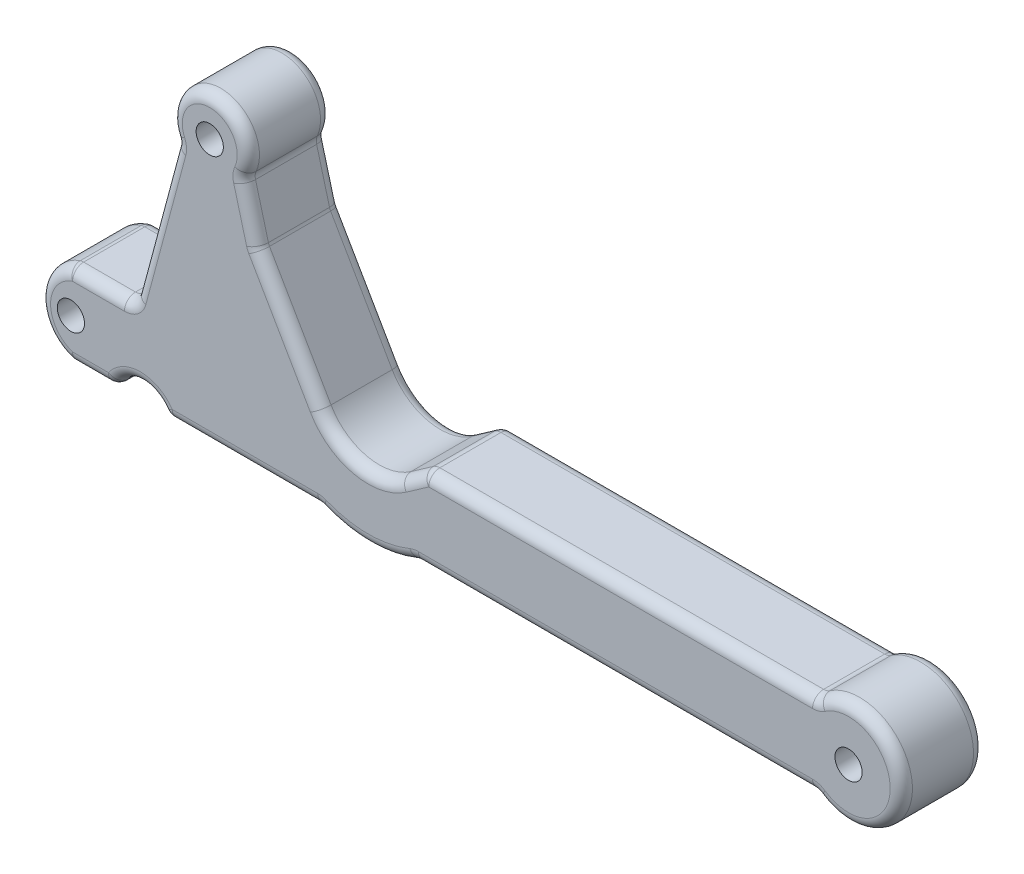
SolidWorks part; units mm, degrees
ref_plane "Front Plane" through (0, 0, 0) normal (0, 0, 1) x (1, 0, 0)
ref_plane "Top Plane" through (0, 0, 0) normal (0, 1, 0) x (1, 0, 0)
ref_plane "Right Plane" through (0, 0, 0) normal (1, 0, 0) x (0, 0, -1)
sketch "Sketch2" plane through (0, 0, 0) normal (0, 0, 1) x (1, 0, 0)
  line L0 (-88.9, 0) -> (88.9, 0) construction
  line L5 (88.9, 0) -> (-88.9, 0) construction
  line L6 (-88.9, 9.525) -> (88.9, 9.525)
  line L7 (-88.9, -9.525) -> (88.9, -9.525)
  line L8 (-63.2223, 52.4271) -> (-74.7179, 9.525)
  line L10 (-39.5821, 9.525) -> (-51.0777, 52.4271)
  line L11 (-46.1887, 34.1811) -> (-31.9535, 9.525)
  line L12 (-13.6706, 5.4718) -> (-7.882, 9.525)
  circle A8 centre (-88.9, 0) radius 3.1115
  circle A9 centre (88.9, 0) radius 3.1115
  circle A10 centre (-57.15, 50.8) radius 3.1115
  arc A11 (-88.9, 9.525) -> (-88.9, -9.525) centre (-88.9, 0) ccw
  arc A12 (88.9, -9.525) -> (88.9, 9.525) centre (88.9, 0) ccw
  arc A13 (-63.2223, 52.4271) -> (-51.0777, 52.4271) centre (-57.15, 50.8) cw
  arc A14 (-78.8449, -9.525) -> (-67.2051, -9.525) centre (-73.025, -12.065) cw
  arc A15 (79.375, -9.525) -> (69.215, -9.525) centre (74.295, -13.335) ccw
  arc A16 (-31.9535, 9.525) -> (-9.9565, 9.525) centre (-20.955, 15.875) ccw
  arc A17 (-88.9, -9.525) -> (-88.9, 9.525) centre (-86.1791, 0) cw
  arc A18 (88.9, -9.525) -> (88.9, 9.525) centre (86.1791, 0) ccw construction
  arc A19 (-31.9535, -9.525) -> (-9.9565, -9.525) centre (-20.955, 15.875) ccw
  arc A20 (81.4947, -9.525) -> (81.4947, 9.525) centre (88.9, 0) ccw
  arc A21 (-64.8259, 46.4425) -> (-49.4741, 46.4425) centre (-57.15, 50.8) cw
  point P5 (0, 0)
  point P8 (0, 0)
  point P30 (-20.955, 3.175)
  dimension "D1" = 6.223
  dimension "D9" = 6.35
  dimension "D11" = 6.35
  dimension "D16" = 12.7
  dimension "D18" = 9.906
  dimension "D2" = 177.8
  dimension "D3" = 31.75
  dimension "D4" = 50.8
  dimension "D5" = 19.05
  dimension "D6" = 3.175
  dimension "D7" = 75
  dimension "D8" = 15.875
  dimension "D10" = 2.54
  dimension "D12" = 3.81
  dimension "D13" = 14.605
  dimension "D14" = 6.35
  dimension "D15" = 67.945
  dimension "D17" = 35
  dimension "D19" = 2.54
  dimension "D20" = 2.54
extrude "Boss-Extrude1" add sketch "Sketch2" along normal mid plane 19.05 contours L7 A18 L6 L12 A16 A17 A14 A15 A8 A9 | L6 A16 | A16 L12 L6 | L7 A15 | L7 A20 L6 A12 region at (2.0697, -0.0891, 0) region at (-20.955, 6.9212, 0) region at (-10.0669, 8.4441, 0) region at (100.6549, 0, 0) region at (74.295, -8.4893, 0)
extrude "Boss-Extrude2" add sketch "Sketch2<4>" along direction (0, 0, 1) on the side of the normal mid plane 19.05 contours A13 L8 L6 L10 A10 | L11 L10 L6 | L7 A15 | L7 A19 | A21 L8 A13 L10 region at (-57.15, 27.9044, 0) region at (-39.2415, 17.7437, 0) region at (-57.15, 59.4062, 0) region at (-20.955, -10.4399, 0) region at (74.295, -8.4893, 0)
sketch "Sketch2<4>" plane through (0, 0, 0) normal (0, 0, 1) x (1, 0, 0) same geometry as "Sketch2"
extrude "Cut-Extrude1" cut sketch "Sketch2<5>" against normal through all both and the other way through all contours L6 A16 | A16 L12 L6 | A14 L7 region at (-73.025, -7.9534, 0) region at (-20.955, 6.9212, 0) region at (-10.0669, 8.4441, 0)
sketch "Sketch2<5>" plane through (0, 0, 0) normal (0, 0, 1) x (1, 0, 0) same geometry as "Sketch2"
fillet "Fillet1" [suppressed] radius 2.54
fillet "Fillet2" [suppressed] radius 2.54
fillet "Fillet3" radius 2.54 43 edges at (-57.15, 59.6265, -9.525) (-64.8259, 46.4425, 0) (-69.7719, 27.9837, -9.525) (-57.15, 59.6265, 9.525) (-49.4741, 46.4425, 0) (-47.8314, 40.3118, -9.525) (-74.7179, 9.525, 0) (-69.7719, 27.9837, 9.525) (-81.8089, 9.525, -9.525) (-47.8314, 40.3118, 9.525) (-46.1887, 34.1811, 0) (-39.0711, 21.853, -9.525) (-81.8089, 9.525, 9.525) (-88.9, 9.525, 0) (-96.0851, 0, -9.525) (-39.0711, 21.853, 9.525) (-23.7038, 3.476, -9.525) (-96.0851, 0, 9.525) (-88.9, -9.525, 0) (-83.8724, -9.525, -9.525) (-23.7038, 3.476, 9.525) (-10.7763, 7.4984, -9.525) (-78.8449, -9.525, 0) (-83.8724, -9.525, 9.525) (-73.025, -5.715, -9.525) (-7.882, 9.525, 0) (-10.7763, 7.4984, 9.525) (36.8064, 9.525, -9.525) (-67.2051, -9.525, 0) (-73.025, -5.715, 9.525) (-49.5793, -9.525, -9.525) (81.4947, 9.525, 0) (36.8064, 9.525, 9.525) (100.965, 0, -9.525) (-20.955, -11.804, -9.525) (35.7691, -9.525, -9.525) (-49.5793, -9.525, 9.525) (-31.9535, -9.525, 0) (100.965, 0, 9.525) (81.4947, -9.525, 0) (-9.9565, -9.525, 0) (-20.955, -11.804, 9.525) (35.7691, -9.525, 9.525)
fillet "Fillet4" [suppressed] radius 2.54
equation "\"D20@Sketch2\"=\"D19@Sketch2\""
